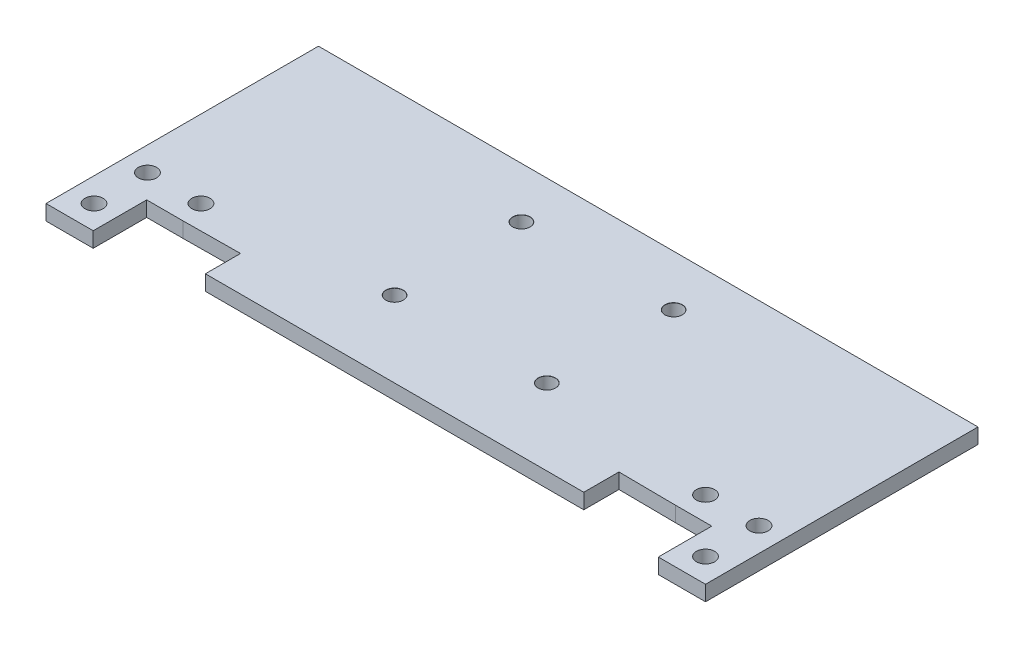
SolidWorks part; units mm, degrees
ref_plane "Front Plane" through (0, 0, 0) normal (0, 0, 1) x (1, 0, 0)
ref_plane "Top Plane" through (0, 0, 0) normal (0, 1, 0) x (1, 0, 0)
ref_plane "Right Plane" through (0, 0, 0) normal (1, 0, 0) x (0, 0, -1)
sketch "Sketch1" plane through (0, 0, 0) normal (1, 0, 0) x (0, 0, -1)
  line L2 (0, 3) -> (50, 3)
  line L6 (0, 0) -> (50, 0)
  line L7 (50, 0) -> (50, 3)
  line L8 (0, 3) -> (0, 0)
  dimension "D3" = 50
  dimension "D6" = 3
extrude "Boss-Extrude1" add sketch "Sketch1" along normal blind 130
hole_wizard "M3 Clearance Hole2" positions "Sketch5" profile "Sketch6" hole size "M3" standard "ANSI Metric" end condition through all
sketch "Sketch5" plane through (0, 3, 0) normal (0, 1, 0) x (1, 0, 0)
  line L0 (65, 50) -> (65, 40) construction
  line L1 (130, 50) -> (0, 50) construction
  line L3 (50, 40) -> (80, 40) construction
  line L4 (80, 40) -> (80, 15) construction
  line L5 (80, 15) -> (50, 15) construction
  line L6 (50, 15) -> (50, 40) construction
  point P9 (50, 40)
  point P11 (80, 40)
  point P13 (50, 15)
  point P15 (80, 15)
  point P25 (65, 40)
  dimension "D1" = 30
  dimension "D2" = 25
  dimension "D3" = 10
sketch "Sketch6" plane through (80, 3, -15) normal (1, 0, 0) x (0, 0, 1)
  line L0 (0, 0) -> (0, 3)
  line L1 (0, 3) -> (1.7, 3)
  line L2 (1.7, 3) -> (1.7, 0.025)
  line L3 (1.7, 0.025) -> (1.725, 0)
  line L5 (1.725, 0) -> (0, 0)
  line L6 (-1.7, 0.025) -> (-1.725, 0) construction
  line L11 (0, -6.35) -> (0, 107.95) construction
  dimension "Thru Hole Dia." = 3.4
  dimension "Thru Hole Depth" = 3
  dimension "Near C'Sink Dia." = 3.45
  dimension "Near C'Sink Angle" = 90
sketch "Sketch7" plane through (0, 0, 0) normal (0, -1, 0) x (1, 0, 0)
  line L0 (130, 0) -> (0, 0) construction
  line L1 (130, 0) -> (0, 0)
  line L2 (108.1956, 0) -> (108.1956, 3.7101)
  line L3 (108.1956, 3.7101) -> (130, 3.7101)
  line L4 (130, 16.7101) -> (130, -16.2899) construction
  line L5 (130, 3.7101) -> (130, 0)
  line L6 (125.2699, -1.02) -> (130, -1.02) construction
  line L7 (130, 0) -> (130, -50) construction
  line L8 (119.0978, 3.7101) -> (119.0978, -1.02) construction
  line L9 (120.4956, -6.6297) -> (120.4956, 8.0593) construction
  line L10 (120.4956, -6.6297) -> (120.4956, 8.0593) construction
  line L11 (65, 0) -> (65, -50) construction
  line L12 (130, -50) -> (0, -50) construction
  line L13 (0, 3.7101) -> (0, 0)
  line L14 (21.8044, 3.7101) -> (0, 3.7101)
  line L15 (21.8044, 0) -> (21.8044, 3.7101)
  circle A0 centre (125.2699, -1.02) radius 1.8 construction
  circle A1 centre (125.2699, -1.02) radius 1.8 construction
  line M17 (130, 0) -> (0, 0)
  dimension "D1" = 12.3
extrude "Boss-Extrude2" add sketch "Sketch7" against normal up to surface (3 mm away) contours L5 L3 L2 M17 | L15 L14 L13 M17 region at (10.9022, 0, 1.8551) region at (119.0978, 0, 1.8551) up to face at (50, 3, -38.275)
sketch "Sketch9" plane through (0, 3, 0) normal (0, 1, 0) x (1, 0, 0)
  line L0 (120.4956, 6.6297) -> (113.4956, 6.6297) construction
  line L1 (120.4956, 6.6297) -> (120.4956, -8.0593) construction
  line L2 (120.4956, 6.6297) -> (113.4956, 6.6297)
  line L3 (120.4956, 6.6297) -> (120.4956, -8.0593)
  line L4 (102.4956, -2.7203) -> (102.4956, 6.7276) construction
  line L5 (102.4956, -2.7203) -> (102.4956, 6.7276)
  line L6 (113.4956, 6.6297) -> (102.4956, 6.7276)
  line L7 (102.4956, -2.7203) -> (120.4956, -8.0593)
  line L8 (102.2956, -2.8696) -> (102.2956, 6.9294)
  line L9 (113.4965, 6.8297) -> (102.2956, 6.9294)
  line L10 (120.6956, 6.8297) -> (113.4965, 6.8297)
  line L11 (120.6956, 6.8297) -> (120.6956, -8.3273)
  line L12 (102.2956, -2.8696) -> (120.6956, -8.3273)
  line L13 (108.1956, 0) -> (21.8044, 0) construction
  line L14 (130, 50) -> (0, 50) construction
  line L15 (108.1956, 0) -> (21.8044, 0) construction
  line L16 (130, 50) -> (0, 50) construction
  line L17 (65, 50) -> (65, 0) construction
  line L18 (9.3044, 6.8297) -> (9.3044, -8.3273)
  line L19 (9.3044, 6.8297) -> (16.5035, 6.8297)
  line L20 (16.5035, 6.8297) -> (27.7044, 6.9294)
  line L21 (27.7044, -2.8696) -> (27.7044, 6.9294)
  line L22 (27.7044, -2.8696) -> (9.3044, -8.3273)
  line M8 (21.8044, -3.7101) -> (21.8044, 0)
  line M9 (21.8044, 0) -> (108.1956, 0)
  line M10 (108.1956, 0) -> (108.1956, -3.7101)
  dimension "D1" = 0.2
extrude "Cut-Extrude1" cut sketch "Sketch9" against normal through all contours L2 L6 L5 L3 M9 | L5 L7 L3 M9 | L8 L12 L11 L3 L7 L5 M10 M9 | L11 L10 L9 L8 L5 L6 L2 L3 M9 | L21 L20 L19 L18 M9 | L22 L21 L18 M9 M8 region at (112.147, 3, -0.5364) region at (102.3195, 3, -3.4647) region at (17.846, 3, -0.5312)
sketch "Sketch10" plane through (0, 3, 0) normal (0, 1, 0) x (1, 0, 0)
  point P0 (125.2699, 1.02)
  point P3 (125.2699, 11.5598)
  point P6 (114.7301, 11.5598)
hole_wizard "M3 Clearance Hole3" positions "Sketch10" profile "Sketch11" hole size "M3" standard "ANSI Metric" end condition through all
sketch "Sketch11" plane through (125.2699, 3, -1.02) normal (1, 0, 0) x (0, 0, 1)
  line L0 (0, 0) -> (0, 3)
  line L1 (0, 3) -> (1.8, 3)
  line L2 (1.8, 3) -> (1.8, 0)
  line L5 (1.8, 0) -> (0, 0)
  line L11 (0, -6.35) -> (0, 107.95) construction
  dimension "Thru Hole Dia." = 3.6
  dimension "Thru Hole Depth" = 3
ref_plane "Plane1" through (65, 0, 0) normal (1, 0, 0) x (0, 0, -1)
mirror "Mirror1" about plane through (65, 0, 0) normal (1, 0, 0) of "M3 Clearance Hole3"
